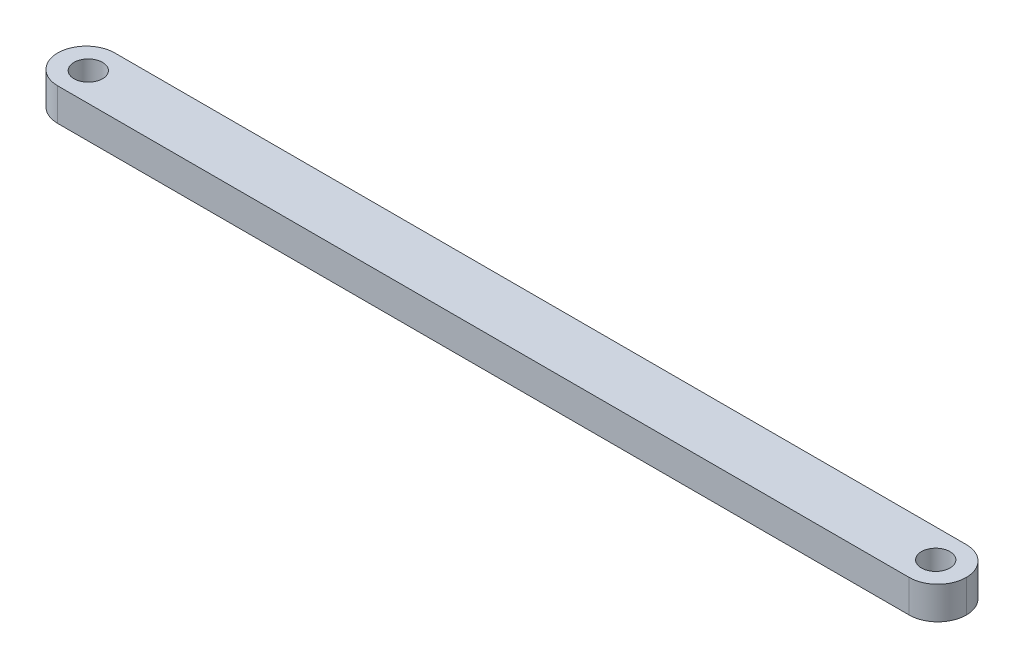
SolidWorks part; units mm, degrees
ref_plane "Front Plane" through (0, 0, 0) normal (0, 0, 1) x (1, 0, 0)
ref_plane "Top Plane" through (0, 0, 0) normal (0, 1, 0) x (1, 0, 0)
ref_plane "Right Plane" through (0, 0, 0) normal (1, 0, 0) x (0, 0, -1)
sketch "Sketch1" plane through (0, 0, 0) normal (0, 1, 0) x (1, 0, 0)
  line L1 (-55.75, 3.5) -> (55.75, 3.5)
  line L2 (-55.75, 3.5) -> (-55.75, -3.5)
  line L3 (-55.75, -3.5) -> (55.75, -3.5)
  line L4 (55.75, 3.5) -> (55.75, -3.5)
  line L5 (-55.75, 3.5) -> (55.75, -3.5) construction
  line L6 (-55.75, -3.5) -> (55.75, 3.5) construction
  point P0 (0, 0)
  dimension "D1" = 7
  dimension "D2" = 111.5
extrude "Boss-Extrude1" add sketch "Sketch1" along normal blind 4
sketch "Sketch2" plane through (0, 4, 0) normal (0, 1, 0) x (1, 0, 0)
  line L0 (0, 0) -> (-52, 0) construction
  line L1 (0, 0) -> (52, 0) construction
  circle A0 centre (-52, 0) radius 1.75
  circle A1 centre (52, 0) radius 1.75
  dimension "D3" = 3.5
  dimension "D4" = 3.5
  dimension "D1" = 52
  dimension "D2" = 52
extrude "Cut-Extrude4" cut sketch "Sketch2" against normal through all
fillet "Fillet1" radius 3.5 4 edges at (55.75, 2, -3.5) (55.75, 2, 3.5) (-55.75, 2, 3.5) (-55.75, 2, -3.5)
